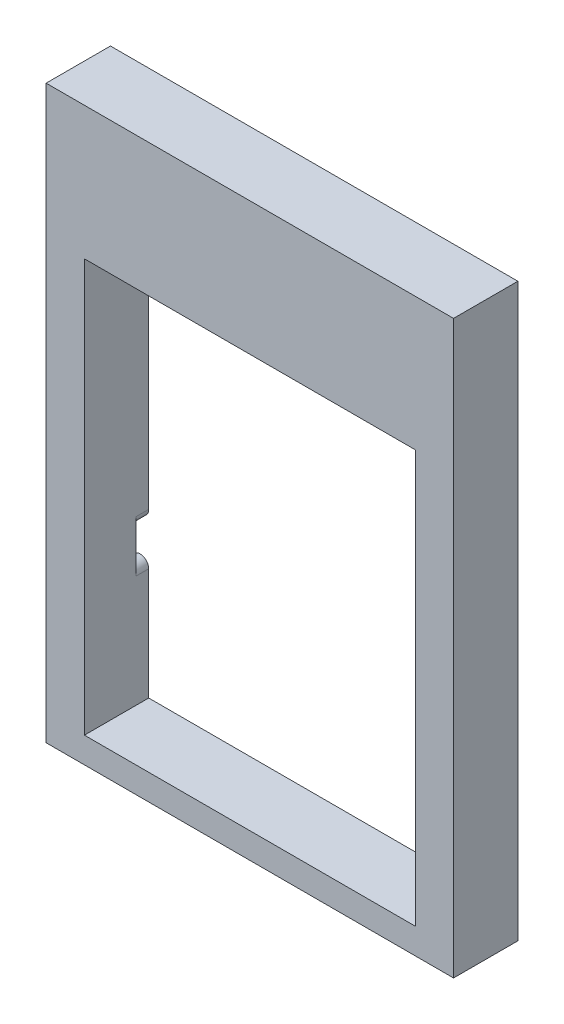
SolidWorks part; units mm, degrees
ref_plane "前视基准面" through (0, 0, 0) normal (0, 0, 1) x (1, 0, 0)
ref_plane "上视基准面" through (0, 0, 0) normal (0, 1, 0) x (1, 0, 0)
ref_plane "右视基准面" through (0, 0, 0) normal (1, 0, 0) x (0, 0, -1)
other "Configuration Table"
sketch "Model" plane through (0, 0, 0) normal (0, 0, 1) x (1, 0, 0)
  line L1 (93.6602, 124.9846) -> (187.8095, 124.9846)
  line L4 (185.3095, -8.2149) -> (96.1602, -8.2149)
  line L6 (188.2349, 124.9846) -> (93.2349, 124.9846)
  line L7 (93.2349, 124.9846) -> (93.2349, -8.2149)
  line L8 (93.2349, -8.2149) -> (188.2349, -8.2149)
  line L9 (188.2349, -8.2149) -> (188.2349, 124.9846)
  line L166 (179.3095, -2.2149) -> (102.1602, -2.2149)
  line L168 (102.1602, 93.9846) -> (179.3095, 93.9846)
  line L172 (102.1602, -2.2149) -> (102.1602, 93.9846)
  line L173 (179.3095, -2.2149) -> (179.3095, 93.9846)
  line L174 (179.3095, -2.2149) -> (179.3095, 93.9846)
  line L175 (185.3095, -8.2149) -> (185.3095, 93.9846) construction
  line L176 (96.1602, -8.2149) -> (96.1602, 93.9846) construction
  point P1 (0, 0)
  point P4 (140.7349, 124.9846)
  dimension "D1" = 6
  dimension "D2" = 95
extrude "凸台-拉伸1" add sketch "Model" along normal blind 15 contours L4 L1 L173 L166 L172 L168 region at (140.7349, 123.3485, 0)
sketch "草图1" plane through (0, 0, 0) normal (0, 0, -1) x (-1, 0, 0)
  line L0 (-179.3095, 118.9846) -> (-179.3095, -2.1894) construction
  line L1 (-183.3095, 97.3849) -> (-183.3095, 94.3849) construction
  line L2 (-183.3095, 79.3849) -> (-183.3095, 82.3849) construction
  line L3 (-185.3095, 79.3849) -> (-185.3095, 97.3849) construction
  line L4 (-185.3095, 97.3849) -> (-185.3095, 79.3849)
  line L5 (-183.3095, 79.3849) -> (-183.3095, 82.3849)
  line L6 (-183.3095, 94.3849) -> (-183.3095, 97.3849)
  line L8 (-185.3095, 38.8849) -> (-185.3095, 20.8849) construction
  line L9 (-185.3095, 38.8849) -> (-185.3095, 20.8849)
  line L10 (-183.3095, 20.8849) -> (-183.3095, 23.8849)
  line L11 (-183.3095, 35.8849) -> (-183.3095, 38.8849)
  line L13 (-140.7349, 124.9846) -> (-140.7349, -8.2149) construction
  line L14 (-188.2349, 124.9846) -> (-93.2349, 124.9846) construction
  line L15 (-93.2349, -8.2149) -> (-188.2349, -8.2149) construction
  line L17 (-98.1602, 35.8849) -> (-98.1602, 38.8849)
  line L18 (-98.1602, 20.8849) -> (-98.1602, 23.8849)
  line L19 (-96.1602, 38.8849) -> (-96.1602, 20.8849)
  line L21 (-98.1602, 94.3849) -> (-98.1602, 97.3849)
  line L22 (-98.1602, 79.3849) -> (-98.1602, 82.3849)
  line L23 (-96.1602, 97.3849) -> (-96.1602, 79.3849)
  line L24 (-102.1602, -2.2149) -> (-102.1602, 93.9846) construction
  line L25 (-179.3095, 118.9846) -> (-102.1602, 118.9846)
  line L26 (-179.3095, 118.9846) -> (-179.3095, 94.3849)
  line L27 (-179.3095, -1.9999) -> (-102.1602, -1.9999)
  line L28 (-102.1602, 118.9846) -> (-102.1602, 94.3849)
  line L29 (-179.3095, 23.8849) -> (-179.3095, -1.9999)
  line L30 (-102.1602, 23.8849) -> (-102.1602, -1.9999)
  line L31 (-102.1602, 82.3849) -> (-102.1602, 35.8849)
  line L32 (-179.3095, 82.3849) -> (-179.3095, 35.8849)
  arc A0 (-179.3095, 94.3849) -> (-183.3095, 94.3849) centre (-181.3095, 94.3849) cw
  arc A1 (-183.3095, 94.3849) -> (-179.3095, 94.3849) centre (-181.3095, 94.3849) ccw construction
  arc A2 (-179.3095, 82.3849) -> (-183.3095, 82.3849) centre (-181.3095, 82.3849) ccw
  arc A3 (-183.3095, 79.3849) -> (-185.3095, 79.3849) centre (-184.3095, 79.3849) cw
  arc A4 (-185.3095, 79.3849) -> (-183.3095, 79.3849) centre (-184.3095, 79.3849) ccw construction
  arc A5 (-183.3095, 97.3849) -> (-185.3095, 97.3849) centre (-184.3095, 97.3849) ccw
  arc A6 (-183.3095, 97.3849) -> (-185.3095, 97.3849) centre (-184.3095, 97.3849) ccw construction
  arc A7 (-183.3095, 35.8849) -> (-179.3095, 35.8849) centre (-181.3095, 35.8849) ccw
  arc A8 (-183.3095, 23.8849) -> (-179.3095, 23.8849) centre (-181.3095, 23.8849) cw
  arc A9 (-179.3095, 23.8849) -> (-183.3095, 23.8849) centre (-181.3095, 23.8849) ccw construction
  arc A10 (-185.3095, 20.8849) -> (-183.3095, 20.8849) centre (-184.3095, 20.8849) ccw
  arc A11 (-185.3095, 20.8849) -> (-183.3095, 20.8849) centre (-184.3095, 20.8849) ccw construction
  arc A12 (-183.3095, 38.8849) -> (-185.3095, 38.8849) centre (-184.3095, 38.8849) ccw
  arc A13 (-183.3095, 38.8849) -> (-185.3095, 38.8849) centre (-184.3095, 38.8849) ccw construction
  arc A14 (-98.1602, 38.8849) -> (-96.1602, 38.8849) centre (-97.1602, 38.8849) cw
  arc A15 (-96.1602, 20.8849) -> (-98.1602, 20.8849) centre (-97.1602, 20.8849) cw
  arc A16 (-98.1602, 23.8849) -> (-102.1602, 23.8849) centre (-100.1602, 23.8849) ccw
  arc A17 (-98.1602, 35.8849) -> (-102.1602, 35.8849) centre (-100.1602, 35.8849) cw
  arc A18 (-98.1602, 97.3849) -> (-96.1602, 97.3849) centre (-97.1602, 97.3849) cw
  arc A19 (-98.1602, 79.3849) -> (-96.1602, 79.3849) centre (-97.1602, 79.3849) ccw
  arc A20 (-102.1602, 82.3849) -> (-98.1602, 82.3849) centre (-100.1602, 82.3849) cw
  arc A21 (-102.1602, 94.3849) -> (-98.1602, 94.3849) centre (-100.1602, 94.3849) ccw
extrude "切除-拉伸1" cut sketch "草图1" against normal blind 3
